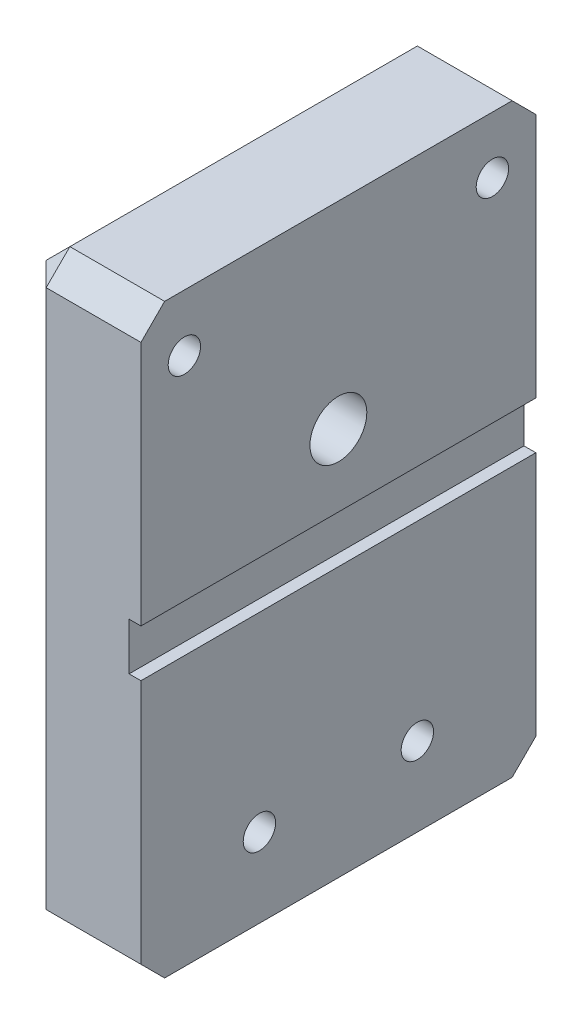
SolidWorks part; units mm, degrees
ref_plane "Front Plane" through (0, 0, 0) normal (0, 0, 1) x (1, 0, 0)
ref_plane "Top Plane" through (0, 0, 0) normal (0, 1, 0) x (1, 0, 0)
ref_plane "Right Plane" through (0, 0, 0) normal (1, 0, 0) x (0, 0, -1)
sketch "Sketch1" plane through (0, 0, 0) normal (0, 0, 1) x (1, 0, 0)
  line L2 (0, 0) -> (0, -74.2)
  line L10 (-15, -74.2) -> (-15, 0)
  line L12 (-15, 0) -> (0, 0)
  line L13 (0, -74.2) -> (-15, -74.2)
  dimension "D1" = 15
  dimension "D2" = 74.2
extrude "Boss-Extrude1" add sketch "Sketch1" along normal blind 50
sketch "Sketch4" plane through (-15, 0, 0) normal (-1, 0, 0) x (0, 0, 1)
  line L0 (0, 0) -> (50, -50) construction
  line L1 (50, 0) -> (50, -74.2) construction
  line L3 (50, 0) -> (0, 0) construction
  circle A0 centre (25, -25) radius 18 construction
  circle A1 centre (43, -25) radius 2.5
  circle A2 centre (41.2174, -32.8099) radius 2.5
  circle A3 centre (36.2228, -39.073) radius 2.5
  circle A4 centre (29.0054, -42.5487) radius 2.5
  circle A5 centre (20.9946, -42.5487) radius 2.5
  circle A6 centre (13.7772, -39.073) radius 2.5
  circle A7 centre (8.7826, -32.8099) radius 2.5
  circle A8 centre (7, -25) radius 2.5
  circle A9 centre (8.7826, -17.1901) radius 2.5
  circle A10 centre (13.7772, -10.927) radius 2.5
  circle A11 centre (20.9946, -7.4513) radius 2.5
  circle A12 centre (29.0054, -7.4513) radius 2.5
  circle A13 centre (36.2228, -10.927) radius 2.5
  circle A14 centre (41.2174, -17.1901) radius 2.5
  dimension "D2" = 5
  dimension "D4" = 36
  dimension "D1" = 45
  dimension "D5" = 25.714
  dimension "D3" = 14
extrude "Cut-Extrude4" cut sketch "Sketch4" against normal blind 4
chamfer "Chamfer2" distance 0.8 angle 45 14 edges at (-15, -27.5, 43) (-15, -19.6901, 41.2174) (-15, -13.427, 36.2228) (-15, -9.9513, 29.0054) (-15, -9.9513, 20.9946) (-15, -13.427, 13.7772) (-15, -19.6901, 8.7826) (-15, -27.5, 7) (-15, -35.3099, 8.7826) (-15, -41.573, 13.7772) (-15, -45.0487, 20.9946) (-15, -45.0487, 29.0054) (-15, -35.3099, 41.2174) (-15, -41.573, 36.2228)
sketch "Sketch5" plane through (-15, 0, 0) normal (-1, 0, 0) x (0, 0, 1)
  line L0 (13.7772, -39.073) -> (36.2228, -10.927) construction
  circle A0 centre (25, -25) radius 3.6
  dimension "D1" = 7.2
extrude "Cut-Extrude5" cut sketch "Sketch5" against normal up to surface (15 mm away) up to face at (0, -37.1, 25)
chamfer "Chamfer3" distance 1.5 angle 45 1 edges at (-15, -28.6, 25)
sketch "Sketch6" plane through (0, 0, 50) normal (0, 0, 1) x (1, 0, 0)
  line L0 (0, -74.2) -> (0, 0) construction
  line L1 (0, -34.1) -> (-1.5, -34.1)
  line L2 (0, -34.1) -> (0, -40.1)
  line L3 (0, -40.1) -> (-1.5, -40.1)
  line L4 (-1.5, -34.1) -> (-1.5, -40.1)
  line L9 (0, -37.1) -> (-15, -37.1) construction
  line L10 (-15, 0) -> (-15, -74.2) construction
  point P4 (-1.5, -37.1)
  point P5 (0, 0)
  dimension "D1" = 6
  dimension "D3" = 1.5
extrude "Cut-Extrude6" cut sketch "Sketch6" against normal up to surface (50 mm away) up to face at (-7.5, -37.1, 0)
sketch "Sketch7" plane through (-15, 0, 0) normal (-1, 0, 0) x (0, 0, 1)
  line L0 (25, -35.2) -> (25, -74.2) construction
  line L1 (50, -74.2) -> (0, -74.2) construction
  line L2 (25, -25) -> (50, -25) construction
  line L3 (50, 0) -> (50, -74.2) construction
  circle A0 centre (15, -64.2) radius 3.75
  circle A1 centre (35, -64.2) radius 3.75
  circle A3 centre (5.5, -7.2) radius 3.75
  circle A4 centre (44.5, -7.2) radius 3.75
  dimension "D1" = 7.5
  dimension "D3" = 39
  dimension "D2" = 20
  dimension "D4" = 10
  dimension "D5" = 57
extrude "Cut-Extrude7" cut sketch "Sketch7" against normal blind 5
sketch "Sketch8" plane through (-10, 0, 0) normal (-1, 0, 0) x (0, 0, 1)
  circle A0 centre (35, -64.2) radius 2.05
  circle A1 centre (15, -64.2) radius 2.05
  circle A3 centre (5.5, -7.2) radius 2.05
  circle A4 centre (44.5, -7.2) radius 2.05
  dimension "D1" = 4.1
extrude "Cut-Extrude8" cut sketch "Sketch8" against normal up to surface (10 mm away) up to face at (0, -57.15, 25)
chamfer "Chamfer4" distance 3 angle 45 8 edges at (-7.5, 0, 0) (-7.5, 0, 50) (-7.5, -74.2, 0) (-7.5, -74.2, 50) (-15, 0, 25) (-15, -37.1, 50) (-15, -74.2, 25) (-15, -37.1, 0)
equation "\"diam\"=7.8"
